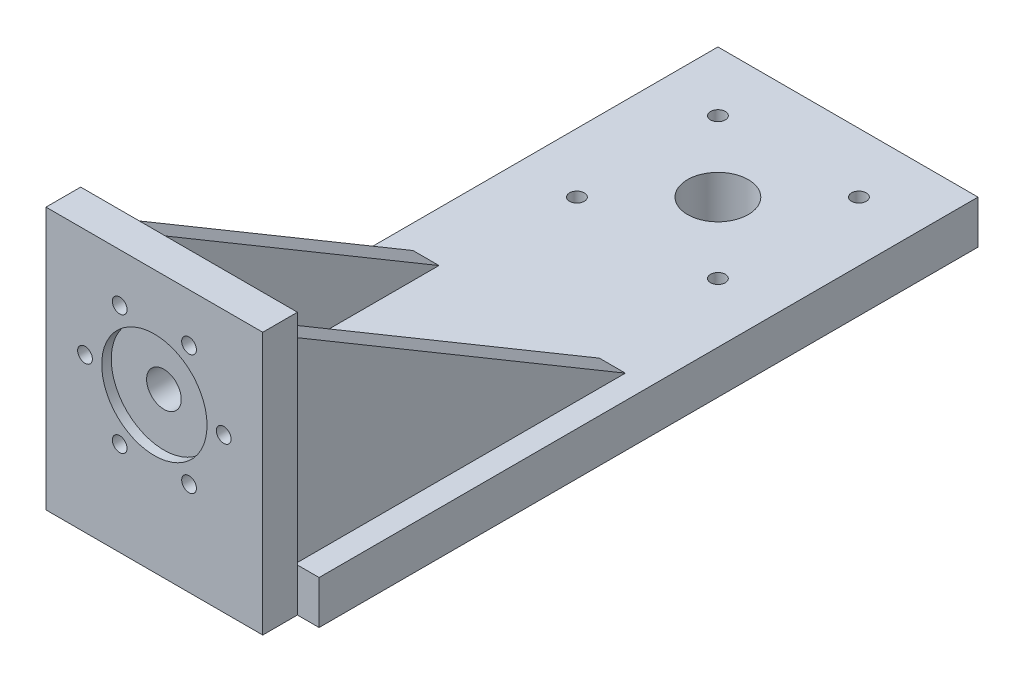
SolidWorks part; units mm, degrees
material "6061-T6 (SS)"
ref_plane "Front Plane" through (0, 0, 0) normal (0, 0, 1) x (1, 0, 0)
ref_plane "Top Plane" through (0, 0, 0) normal (0, 1, 0) x (1, 0, 0)
ref_plane "Right Plane" through (0, 0, 0) normal (1, 0, 0) x (0, 0, -1)
ref_plane "PL_Yaw_Plate_base" through (0, 0, -8) normal (0, 0, 1) x (1, 0, 0)
sketch "SK_Yaw_Plate" plane through (0, 0, -8) normal (0, 0, 1) x (1, 0, 0)
  line L0 (-25, -35.5) -> (25, -35.5)
  line L1 (25, -35.5) -> (25, 25)
  line L2 (25, 25) -> (-25, 25)
  line L3 (-25, 25) -> (-25, -35.5)
  circle A0 centre (16, 0) radius 1.7
  circle A1 centre (8, 13.8564) radius 1.7
  circle A2 centre (-8, 13.8564) radius 1.7
  circle A3 centre (-16, 0) radius 1.7
  circle A4 centre (-8, -13.8564) radius 1.7
  circle A5 centre (8, -13.8564) radius 1.7
  circle A6 centre (0, 0) radius 4
  dimension "D9_SK_Yaw_Plate" = 3.4
  dimension "D11_SK_Yaw_Plate" = 3.4
  dimension "D14_SK_Yaw_Plate" = 3.4
  dimension "D17_SK_Yaw_Plate" = 3.4
  dimension "D19_SK_Yaw_Plate" = 3.4
  dimension "D22_SK_Yaw_Plate" = 3.4
  dimension "D25_SK_Yaw_Plate" = 8
  dimension "P1" = 25
  dimension "P2" = 35.5
  dimension "P3" = 25
  dimension "P4" = 35.5
  dimension "P5" = 25
  dimension "P6" = 25
  dimension "P7" = 25
  dimension "P8" = 25
  dimension "P10" = 16
  dimension "P12" = 8
  dimension "P13" = 13.8564
  dimension "P15" = 8
  dimension "P16" = 13.8564
  dimension "P18" = 16
  dimension "P20" = 8
  dimension "P21" = 13.8564
  dimension "P23" = 8
  dimension "P24" = 13.8564
extrude "Yaw_Plate" add sketch "SK_Yaw_Plate" along normal blind 8
sketch "SK_Yaw_Pilot_Recess" plane through (0, 0, 0) normal (0, 0, 1) x (1, 0, 0)
  circle A0 centre (0, 0) radius 12.15
  dimension "D1_SK_Yaw_Pilot_Recess" = 24.3
extrude "Yaw_Pilot_Recess" cut sketch "SK_Yaw_Pilot_Recess" against normal blind 2.2
ref_plane "PL_Elbow_Plate_base" through (0, -35.5, 0) normal (0, 1, 0) x (1, 0, 0)
sketch "SK_Elbow_Plate" plane through (0, -35.5, 0) normal (0, 1, 0) x (1, 0, 0)
  line L0 (-30, 8) -> (30, 8)
  line L1 (30, 8) -> (30, 160)
  line L2 (30, 160) -> (-30, 160)
  line L3 (-30, 160) -> (-30, 8)
  circle A0 centre (16.2635, 146.2635) radius 1.7
  circle A1 centre (-16.2635, 146.2635) radius 1.7
  circle A2 centre (-16.2635, 113.7365) radius 1.7
  circle A3 centre (16.2635, 113.7365) radius 1.7
  circle A4 centre (0, 130) radius 7
  dimension "D9_SK_Elbow_Plate" = 3.4
  dimension "D12_SK_Elbow_Plate" = 3.4
  dimension "D15_SK_Elbow_Plate" = 3.4
  dimension "D18_SK_Elbow_Plate" = 3.4
  dimension "D21_SK_Elbow_Plate" = 14
  dimension "P1" = 30
  dimension "P2" = 8
  dimension "P3" = 30
  dimension "P4" = 8
  dimension "P5" = 30
  dimension "P6" = 160
  dimension "P7" = 30
  dimension "P8" = 160
  dimension "P10" = 16.2635
  dimension "P11" = 146.2635
  dimension "P13" = 16.2635
  dimension "P14" = 146.2635
  dimension "P16" = 16.2635
  dimension "P17" = 113.7365
  dimension "P19" = 16.2635
  dimension "P20" = 113.7365
  dimension "P22" = 130
extrude "Elbow_Plate" add sketch "SK_Elbow_Plate" along normal blind 10
ref_plane "PL_Gusset_Front_base" through (18.5, 0, 0) normal (1, 0, 0) x (0, 0, -1)
sketch "SK_Gusset_Front" plane through (18.5, 0, 0) normal (1, 0, 0) x (0, 0, -1)
  line L0 (7.5, -26) -> (7.5, 20)
  line L1 (7.5, 20) -> (85, -26)
  line L2 (85, -26) -> (7.5, -26)
  dimension "P1" = 7.5
  dimension "P2" = 26
  dimension "P3" = 7.5
  dimension "P4" = 20
  dimension "P5" = 85
  dimension "P6" = 26
extrude "Gusset_Front" add sketch "SK_Gusset_Front" along normal blind 6
ref_plane "PL_Gusset_Back_base" through (-24.5, 0, 0) normal (1, 0, 0) x (0, 0, -1)
sketch "SK_Gusset_Back" plane through (-24.5, 0, 0) normal (1, 0, 0) x (0, 0, -1)
  line L0 (7.5, -26) -> (7.5, 20)
  line L1 (7.5, 20) -> (85, -26)
  line L2 (85, -26) -> (7.5, -26)
  dimension "P1" = 7.5
  dimension "P2" = 26
  dimension "P3" = 7.5
  dimension "P4" = 20
  dimension "P5" = 85
  dimension "P6" = 26
extrude "Gusset_Back" add sketch "SK_Gusset_Back" along normal blind 6
equation "\"Elbow_z\"= -130"
equation "\"Elbow_plate_t\"= 10"
equation "\"Yaw_plate_t\"= 8"
